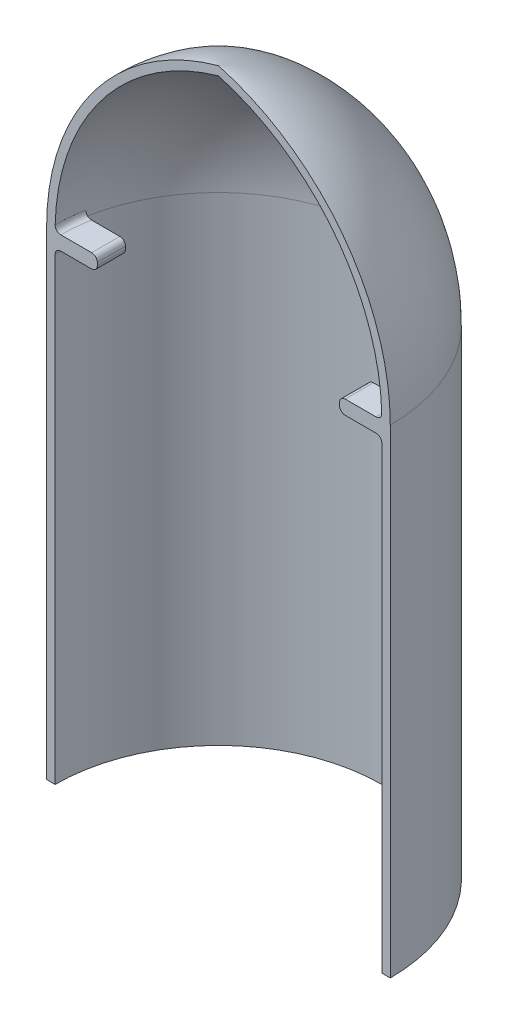
SolidWorks part; units mm, degrees
ref_plane "Front Plane" through (0, 0, 0) normal (0, 0, 1) x (1, 0, 0)
ref_plane "Top Plane" through (0, 0, 0) normal (0, 1, 0) x (1, 0, 0)
ref_plane "Right Plane" through (0, 0, 0) normal (1, 0, 0) x (0, 0, -1)
sketch "Sketch1" plane through (0, 0, 0) normal (0, 0, 1) x (1, 0, 0)
  line L4 (61, 170) -> (61, 0)
  line L5 (0, 246.8846) -> (0, 250)
  line L9 (58, 0) -> (61, 0)
  line L10 (0, 0) -> (0, 250) construction
  line L15 (58, 0) -> (58, 170) construction
  line L16 (61, 0) -> (61, 170) construction
  line L19 (58, 170) -> (58, 0)
  arc A0 (61, 170) -> (0, 250) centre (-21.959, 170) ccw
  arc A1 (58, 170) -> (0, 246.8846) centre (-21.959, 170) ccw
  arc A8 (58, 170) -> (-0.7941, 247.107) centre (-21.959, 170) ccw construction
  point P9 (0, 0)
  point P11 (58, 166.7829)
  point P12 (0, 0)
  point P13 (58, 135.7805)
  point P14 (0, 0)
  point P15 (0, 0)
  point P16 (0, 0)
  point P17 (0, 0)
  dimension "D2" = 170
  dimension "D3" = 80
  dimension "D5" = 61
  dimension "D4" = 3
revolve "Revolve1" add sketch "Sketch1" angle 180 about L10
sketch "Sketch2" plane through (0, 0, 0) normal (0, 0, 1) x (1, 0, 0)
  line L0 (58, 170) -> (43, 170)
  line L1 (-58, 170) -> (58, 170) construction
  line L2 (43, 170) -> (43, 165)
  line L3 (43, 165) -> (58, 165)
  line L4 (58, 170) -> (58, 0) construction
  line L5 (58, 165) -> (58, 170)
  line L6 (0, 251.6085) -> (0, 170) construction
  line L7 (-58, 165) -> (-58, 170)
  line L8 (-58, 170) -> (-43, 170)
  line L9 (-43, 170) -> (-43, 165)
  line L10 (-43, 165) -> (-58, 165)
  point P15 (0, 0)
  dimension "D1" = 15
  dimension "D2" = 5
extrude "Boss-Extrude1" add sketch "Sketch2" against normal blind 10
fillet "Fillet2" radius 2 4 edges at (-57.7824, 170, -5.0188) (-43, 170, -5) (43, 170, -5) (57.7824, 170, -5.0188)
fillet "Fillet3" radius 2 1 edges at (57.7824, 165, -5.0188)
fillet "Fillet4" radius 2 1 edges at (-57.7824, 165, -5.0188)
fillet "Fillet5" radius 2 1 edges at (-43, 165, -5)
fillet "Fillet6" radius 2 1 edges at (43, 165, -5)
